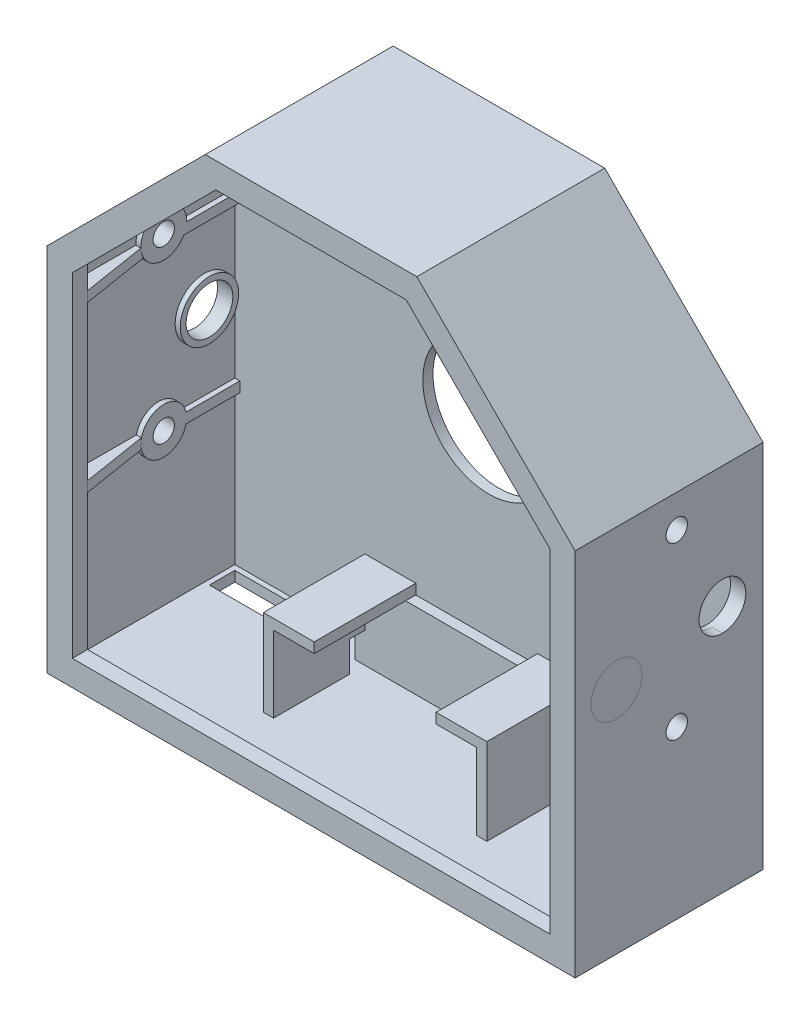
SolidWorks part; units mm, degrees
ref_plane "Face" through (0, 0, 0) normal (0, 0, 1) x (1, 0, 0)
ref_plane "Dessus" through (0, 0, 0) normal (0, 1, 0) x (1, 0, 0)
ref_plane "Droite" through (0, 0, 0) normal (1, 0, 0) x (0, 0, -1)
sketch "Esquisse1" plane through (0, 0, 0) normal (0, 0, 1) x (1, 0, 0)
  line L0 (-50, 20) -> (-20, 50)
  line L1 (-50, -50) -> (50, -50)
  line L2 (-50, -50) -> (-50, 20)
  line L3 (-20, 50) -> (20, 50)
  line L4 (50, -50) -> (50, 20)
  line L5 (-50, -50) -> (50, 50) construction
  line L6 (-50, 50) -> (50, -50) construction
  line L7 (20, 50) -> (50, 20)
  point P0 (0, 0)
  dimension "D1" = 100
  dimension "D2" = 100
extrude "Boss.-Extru.1" add sketch "Esquisse1" along normal blind 35
shell "Coque3" thickness 2 removed face at (0, 6.6667, 35) outward yes
sketch "Esquisse3" plane through (0, 0, 0) normal (0, 0, 1) x (1, 0, 0)
  circle A0 centre (0, 0) radius 13
  dimension "D1" = 26
extrude "Enlèv. mat.-Extru.1" cut sketch "Esquisse3" against normal through all
sketch "Esquisse5" plane through (0, -52, 0) normal (0, -1, 0) x (1, 0, 0)
  line L1 (49, 6) -> (29, 6)
  line L2 (49, 6) -> (49, 1)
  line L3 (49, 1) -> (29, 1)
  line L4 (29, 6) -> (29, 1)
  line L5 (49, 6) -> (29, 1) construction
  line L6 (49, 1) -> (29, 6) construction
  line L7 (-52, -2) -> (52, -2) construction
  line L8 (52, 35) -> (52, -2) construction
  line L9 (0, 40.9279) -> (0, -23.2556) construction
  line L10 (-49, 1) -> (-29, 1)
  line L11 (-29, 6) -> (-29, 1)
  line L12 (-49, 6) -> (-29, 6)
  line L13 (-49, 6) -> (-49, 1)
  point P0 (39, 3.5)
  dimension "D1" = 20
  dimension "D2" = 5
  dimension "D3" = 5.5
  dimension "D4" = 3
extrude "Enlèv. mat.-Extru.3" cut sketch "Esquisse5" against normal up to surface (2 mm away) up to face at (0, -50, 17.5)
sketch "Esquisse6" plane through (-52, 0, 0) normal (-1, 0, 0) x (0, 0, 1)
  line L0 (35, 20.8284) -> (-2, 20.8284) construction
  line L1 (35, 20.8284) -> (35, -52) construction
  circle A0 centre (6, -3.1116) radius 4.6
  dimension "D1" = 9.2
  dimension "D3" = 29
  dimension "D2" = 23.94
extrude "Enlèv. mat.-Extru.4" cut sketch "Esquisse6" against normal through all
sketch "Esquisse7" plane through (-52, 0, 0) normal (-1, 0, 0) x (0, 0, 1)
  line L0 (35, 20.8284) -> (-2, 20.8284) construction
  line L1 (-2, 20.8284) -> (-2, -52) construction
  line L2 (35, -52) -> (-2, -52) construction
  circle A0 centre (15, 14.3884) radius 2.1
  circle A1 centre (15, -19.2) radius 2.1
  point P10 (16.5, -52)
  dimension "D1" = 4.2
  dimension "D2" = 6.44
  dimension "D3" = 17
  dimension "D4" = 4.2
  dimension "D5" = 32.8
  dimension "D6" = 17
extrude "Enlèv. mat.-Extru.5" cut sketch "Esquisse7" against normal through all
sketch "Esquisse8" plane through (0, -50, 0) normal (0, 1, 0) x (1, 0, 0)
  line L0 (0, 0) -> (0, -2.3811) construction
  line L1 (-50, 0) -> (50, 0) construction
  line L2 (0, -47.4999) -> (0, 0) construction
  line L3 (0, -22.3811) -> (0, -47.4999) construction
  line L4 (22, -22.3811) -> (-22, -22.3811)
  line L5 (22, -22.3811) -> (22, -2.3811)
  line L6 (22, -2.3811) -> (-22, -2.3811)
  line L7 (-22, -22.3811) -> (-22, -2.3811)
  dimension "D1" = 20
  dimension "D2" = 44
  dimension "D3" = 22
extrude "Boss.-Extru.2" add sketch "Esquisse8" along normal blind 17
sketch "Esquisse9" plane through (0, 0, 22.3811) normal (0, 0, 1) x (1, 0, 0)
  line L0 (-22, -50) -> (22, -50) construction
  line L1 (20, -50) -> (-20, -50)
  line L2 (20, -50) -> (20, -35)
  line L3 (20, -35) -> (-20, -35)
  line L4 (-20, -50) -> (-20, -35)
  line L5 (22, -33) -> (22, -50) construction
  line L6 (-22, -33) -> (-22, -50) construction
  line L7 (-22, -33) -> (22, -33) construction
  dimension "D1" = 2
  dimension "D2" = 2
  dimension "D3" = 2
extrude "Enlèv. mat.-Extru.7" cut sketch "Esquisse9" against normal blind 18
sketch "Esquisse10" plane through (-20, 0, 0) normal (1, 0, 0) x (0, 0, -1)
  line L1 (-4.3811, -50) -> (-7.3811, -50)
  line L2 (-4.3811, -50) -> (-4.3811, -44)
  line L3 (-4.3811, -44) -> (-7.3811, -44)
  line L4 (-7.3811, -50) -> (-7.3811, -44)
  dimension "D1" = 6
  dimension "D2" = 3
extrude "Enlèv. mat.-Extru.8" cut sketch "Esquisse10" against normal blind 5
sketch "Esquisse12" plane through (-52, 0, 0) normal (-1, 0, 0) x (0, 0, 1)
  circle A0 centre (26.6654, -5.0883) radius 5.6012
  dimension "D1" = 11.2024
sketch "Esquisse13" plane through (52, 0, 0) normal (1, 0, 0) x (0, 0, -1)
  circle A0 centre (-26.8672, -6.9058) radius 5
  dimension "D1" = 10
split line "Ligne de séparation1"
split line "Ligne de séparation3"
sketch "Esquisse17" plane through (0, 0, 35) normal (0, 0, 1) x (1, 0, 0)
  line L21 (50, -50) -> (50, 20) construction
  line L22 (50, -50) -> (50, 20)
  line L23 (-50, -50) -> (50, -50) construction
  line L24 (-50, 20) -> (-50, -50) construction
  line L25 (-20, 50) -> (-50, 20) construction
  line L26 (20, 50) -> (-20, 50) construction
  line L27 (-47, -47) -> (47, -47)
  line L28 (-47, 18.7574) -> (-47, -47)
  line L29 (-18.7574, 47) -> (-47, 18.7574)
  line L30 (47, 18.7574) -> (18.7574, 47)
  line L31 (47, -47) -> (47, 18.7574)
  line L32 (18.7574, 47) -> (-18.7574, 47)
  line L33 (-47, -47) -> (47, -47)
  line L34 (-47, 18.7574) -> (-47, -47)
  line L35 (-18.7574, 47) -> (-47, 18.7574)
  line L36 (47, 18.7574) -> (18.7574, 47)
  line L37 (47, -47) -> (47, 18.7574)
  line L38 (18.7574, 47) -> (-18.7574, 47)
  line L39 (50, 20) -> (20, 50) construction
  line L40 (-50, -50) -> (50, -50)
  line L41 (-50, 20) -> (-50, -50)
  line L42 (-20, 50) -> (-50, 20)
  line L43 (20, 50) -> (-20, 50)
  line L44 (50, 20) -> (20, 50)
  dimension "D1" = 3
extrude "Boss.-Extru.4" add sketch "Esquisse17" against normal blind 3
ref_point "Point1"
ref_plane "Plan1" through (0, 0, 6) normal (0, 0, -1) x (-1, 0, 0)
sketch "Esquisse19" plane through (0, 0, 6) normal (0, 0, -1) x (-1, 0, 0)
  line L1 (-52, -7.7116) -> (-50, -7.7116)
  line L2 (-52, -7.7116) -> (-52, 1.4884)
  line L3 (-52, 1.4884) -> (-50, 1.4884)
  line L4 (-50, -7.7116) -> (-50, 1.4884)
  line L8 (-50, -7.7116) -> (-50, 1.4884) construction
sketch "Esquisse20" plane through (-50, 0, 0) normal (1, 0, 0) x (0, 0, -1)
  circle A0 centre (-15, 14.3884) radius 4.5
  dimension "D1" = 9
sketch "Esquisse22" plane through (-50, 0, 0) normal (1, 0, 0) x (0, 0, -1)
  circle A0 centre (-15, -19.2) radius 4.5
  dimension "D1" = 9
extrude "Boss.-Extru.7" add sketch "Esquisse22" along normal blind 1
sketch "Esquisse24" plane through (-49, 0, 0) normal (1, 0, 0) x (0, 0, -1)
  circle A0 centre (-15, -19.2) radius 2.1
  circle A1 centre (-15, -19.2) radius 2.1 construction
extrude "Enlèv. mat.-Extru.12" cut sketch "Esquisse24" against normal blind 3
extrude "Boss.-Extru.8" add sketch "Esquisse20" along normal blind 1
sketch "Esquisse25" plane through (-50, 0, 0) normal (-1, 0, 0) x (0, 0, 1)
  circle A0 centre (15, 14.3884) radius 2.1
  circle A1 centre (15, 14.3884) radius 2.1 construction
extrude "Enlèv. mat.-Extru.13" cut sketch "Esquisse25" against normal blind 3
sketch "Esquisse26" plane through (50, 0, 0) normal (-1, 0, 0) x (0, 0, 1)
  circle A0 centre (15, 14.3884) radius 4.5
  dimension "D1" = 9
extrude "Boss.-Extru.9" add sketch "Esquisse26" along normal blind 1
sketch "Esquisse27" plane through (50, 0, 0) normal (1, 0, 0) x (0, 0, -1)
  circle A0 centre (-15, 14.3884) radius 2.1
  circle A1 centre (-15, 14.3884) radius 2.1 construction
extrude "Enlèv. mat.-Extru.14" cut sketch "Esquisse27" against normal blind 3
sketch "Esquisse28" plane through (50, 0, 0) normal (-1, 0, 0) x (0, 0, 1)
  circle A0 centre (15, -19.2) radius 4.5
  dimension "D1" = 9
extrude "Boss.-Extru.10" add sketch "Esquisse28" along normal blind 1
sketch "Esquisse29" plane through (49, 0, 0) normal (-1, 0, 0) x (0, 0, 1)
  circle A1 centre (15, -19.2) radius 2.1
  circle A2 centre (15, -19.2) radius 2.1 construction
extrude "Enlèv. mat.-Extru.15" cut sketch "Esquisse29" against normal blind 3
sketch "Esquisse34" plane through (-50, 0, 0) normal (1, 0, 0) x (0, 0, -1)
  circle A0 centre (-6, -3.1116) radius 5.75
  dimension "D1" = 11.5
extrude "Boss.-Extru.16" add sketch "Esquisse34" along normal blind 1
sketch "Esquisse35" plane through (-50, 0, 0) normal (-1, 0, 0) x (0, 0, 1)
  circle A1 centre (6, -3.1116) radius 4.6
  circle A2 centre (6, -3.1116) radius 4.6 construction
extrude "Enlèv. mat.-Extru.19" cut sketch "Esquisse35" against normal blind 1
sketch "Esquisse36" plane through (50, 0, 0) normal (-1, 0, 0) x (0, 0, 1)
  circle A0 centre (6, -3.1116) radius 5.5
  dimension "D1" = 11
extrude "Boss.-Extru.17" add sketch "Esquisse36" along normal blind 1
sketch "Esquisse37" plane through (49, 0, 0) normal (-1, 0, 0) x (0, 0, 1)
  circle A0 centre (6, -3.1116) radius 4.6
  circle A1 centre (6, -3.1116) radius 4.6 construction
extrude "Enlèv. mat.-Extru.20" cut sketch "Esquisse37" against normal blind 1
split line "Ligne de séparation4"
ref_point "Point2"
ref_plane "Plan2" through (0, -19.2, 0) normal (0, 1, 0) x (1, 0, 0)
sketch "Esquisse38" plane through (0, -19.2, 0) normal (0, 1, 0) x (1, 0, 0)
  line L0 (-47, -32) -> (-49, -19.5)
  line L1 (-49, -19.5) -> (-49, -10.5) construction
rib "Nervure3" sketch "Esquisse38" sketch "Esquisse38" thickness 2 extrusion direction parallel to sketch draft on no parameters "D1"=2
sketch "Esquisse39" plane through (-49, 0, 0) normal (1, 0, 0) x (0, 0, -1)
  line L0 (-12.9, -19.2) -> (0, -19.2)
  line L1 (0, 20) -> (0, -50) construction
  line L3 (20.35, -19.2) -> (-20.35, -19.2) construction
  circle A1 centre (-15, -19.2) radius 2.1 construction
rib "Nervure4" sketch "Esquisse39" sketch "Esquisse39" thickness 2 extrusion direction normal to sketch draft on no parameters "D1"=2
sketch "Esquisse40" plane through (0, -33, 0) normal (0, 1, 0) x (1, 0, 0)
  line L0 (22, -2.3811) -> (-22, -2.3811) construction
  line L1 (12, -2.3811) -> (-12, -2.3811)
  line L2 (12, -2.3811) -> (12, -22.3811)
  line L3 (12, -22.3811) -> (-12, -22.3811)
  line L4 (-12, -2.3811) -> (-12, -22.3811)
  line L5 (-22, -22.3811) -> (22, -22.3811) construction
  line L6 (22, -22.3811) -> (22, -2.3811) construction
  point P8 (0, -2.3811)
  dimension "D1" = 10
extrude "Enlèv. mat.-Extru.21" cut sketch "Esquisse40" against normal up to surface (2 mm away) up to face at (0, -35, 13.3811)
mirror "Symétrie1" about plane through (0, 0, 0) normal (1, 0, 0) of "Nervure4", "Nervure3"
ref_plane "Plan3" through (0, -3, 0) normal (0, 1, 0) x (1, 0, 0)
mirror "Symétrie2" about plane through (0, -3, 0) normal (0, 1, 0) of "Symétrie1"
